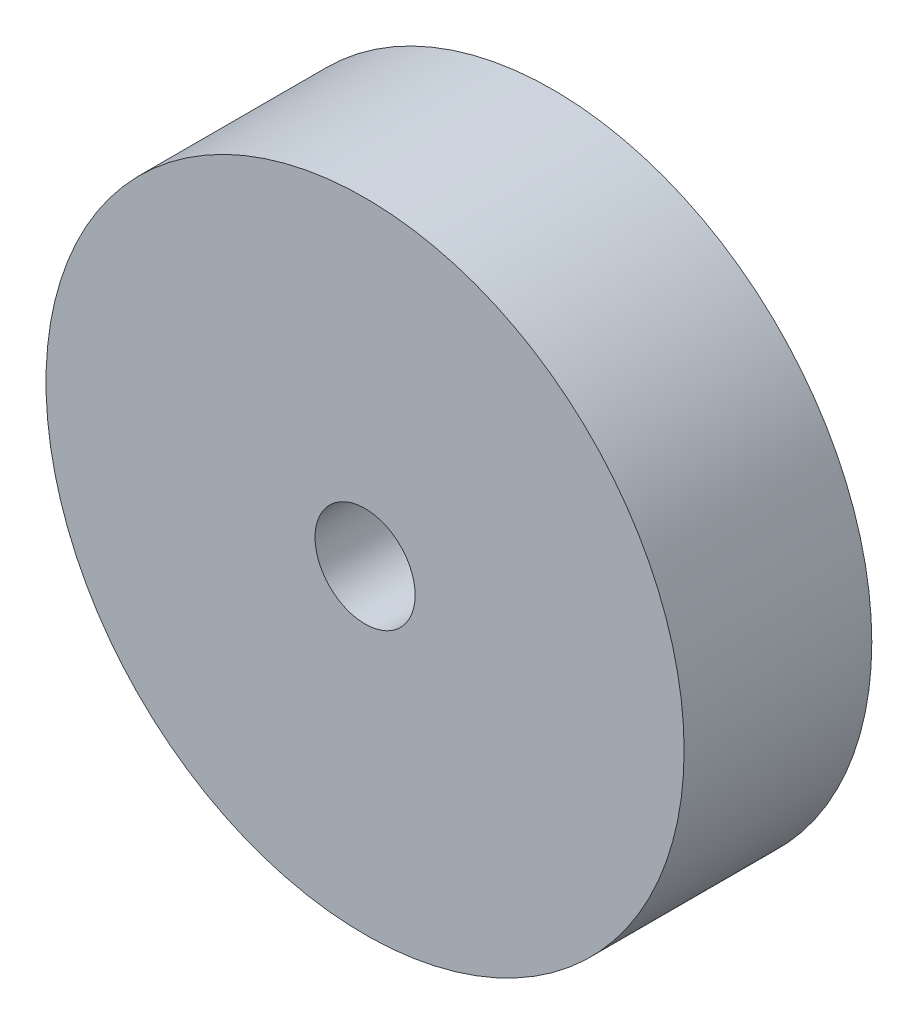
SolidWorks part; units mm, degrees
ref_plane "Front Plane" through (0, 0, 0) normal (0, 0, 1) x (1, 0, 0)
ref_plane "Top Plane" through (0, 0, 0) normal (0, 1, 0) x (1, 0, 0)
ref_plane "Right Plane" through (0, 0, 0) normal (1, 0, 0) x (0, 0, -1)
sketch "Sketch1" plane through (0, 0, 0) normal (0, 0, 1) x (1, 0, 0)
  circle A0 centre (0, 0) radius 25.5
  circle A1 centre (0, 0) radius 4
  dimension "D1" = 51
extrude "Boss-Extrude1" add sketch "Sketch1" along normal blind 15
